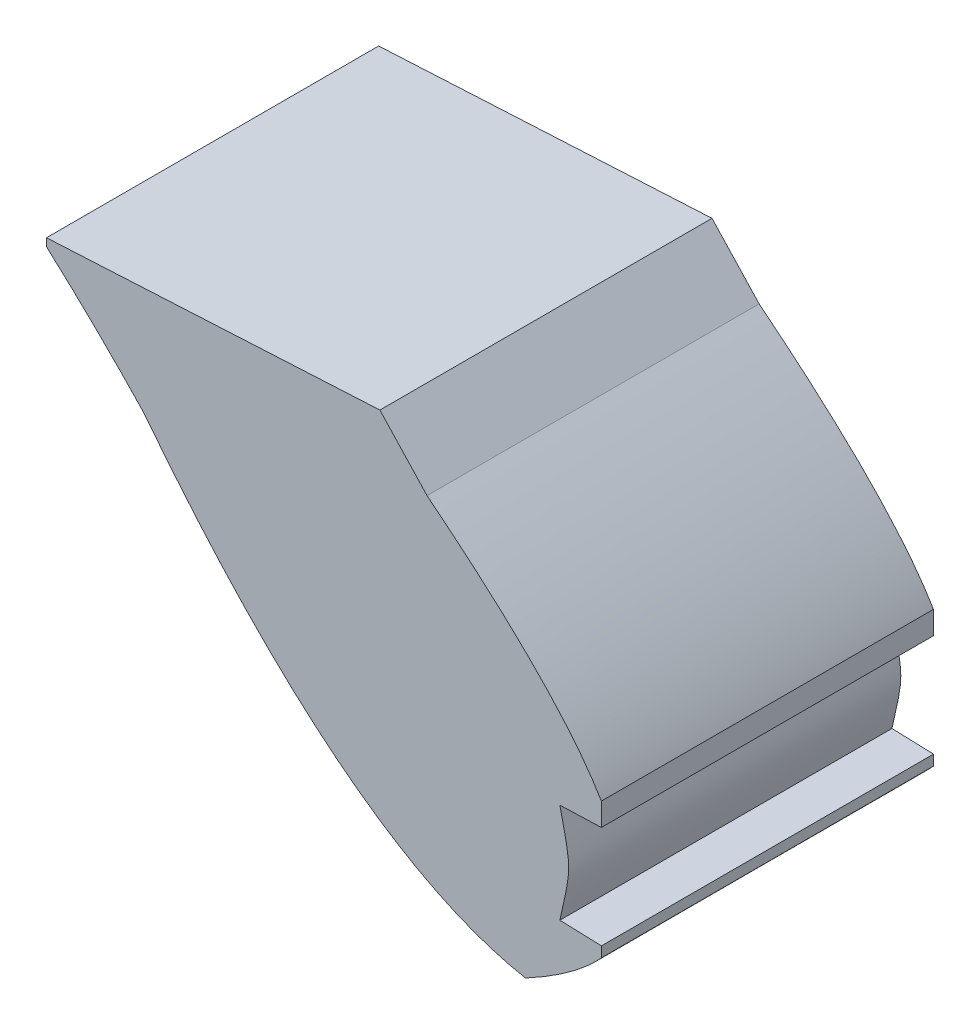
SolidWorks part; units mm, degrees
ref_plane "Alzado" through (0, 0, 0) normal (0, 0, 1) x (1, 0, 0)
ref_plane "Planta" through (0, 0, 0) normal (0, 1, 0) x (1, 0, 0)
ref_plane "Vista lateral" through (0, 0, 0) normal (1, 0, 0) x (0, 0, -1)
sketch "Croquis1" plane through (0, 0, 0) normal (0, 0, 1) x (1, 0, 0)
  line L0 (-8.9818, 12.6082) -> (-23.0359, 11.8716) construction
  line L1 (-8.9818, 12.6082) -> (-23.0359, 11.8716)
  line L2 (-8.9818, 12.6082) -> (-23.0359, 11.8716) construction
  line L4 (-8.9818, 12.6082) -> (-23.0359, 11.8716)
  line L6 (-1.3949, 1.9763) -> (0.3551, 2.2848) construction
  line L7 (-1.3949, 1.9763) -> (0.3551, 2.2848)
  line L8 (0.3551, 2.2848) -> (0.3551, 2.8423) construction
  line L9 (0.3551, 2.2848) -> (0.3551, 3.0015)
  line L10 (0.3551, -2.2848) -> (-1.3949, -2.2237) construction
  line L11 (0.3551, -2.2848) -> (-1.3949, -2.2237)
  line L12 (0.3551, 2.2848) -> (0.3551, -2.2848) construction
  line L13 (0.3551, -2.2848) -> (0.3551, -2.7233)
  line L14 (-8.9818, 12.6082) -> (-6.9949, 10.4774)
  line L15 (-23.0359, 11.5401) -> (-23.0359, 11.8716) construction
  line L16 (-23.0359, 11.5401) -> (-23.0359, 11.8716)
  arc A0 (-18.9452, 7.5409) -> (-23.0359, 11.5401) centre (-69.8841, -40.4718) ccw construction
  arc A1 (-18.9452, 7.5409) -> (-23.0359, 11.5401) centre (-69.8841, -40.4718) ccw
  spline S1 degree 2 poles (-828.7061, 3922.2202) (545.889, -3962.7836) (-262.0834, 3982.5902) knots 0.462185 0.462185 0.462185 0.537731 0.537731 0.537731 weights 1 1 1 only from (-18.9452, 7.5409) to (-2.8466, -5.0591) construction
  spline S2 degree 2 poles (-18.9452, 7.5409) (-10.215, -3.6976) (-2.8466, -5.0591) knots 0.497667 0.497667 0.497667 0.499554 0.499554 0.499554 weights 1 1 1
  spline S3 degree 2 poles (-3804.8689, 1232.5771) (3762.9122, -1369.6643) (-3716.5752, 1504.852) knots 0.462212 0.462212 0.462212 0.537836 0.537836 0.537836 weights 1 1 1 only from (0.3551, 3.0015) to (-6.9949, 10.4774) construction
  spline S4 degree 2 poles (0.3551, 3.0015) (-1.4487, 6.0584) (-6.9949, 10.4774) knots 0.500821 0.500821 0.500821 0.502013 0.502013 0.502013 weights 1 1 1
  spline S5 degree 2 poles (-1.3949, -2.2237) (-0.9075, -0.1237) (-1.3949, 1.9763) knots 0 0 0 1 1 1 weights 1 3.231801 1 construction
  spline S6 degree 2 poles (-1.3949, -2.2237) (-0.9075, -0.1237) (-1.3949, 1.9763) knots 0 0 0 1 1 1 weights 1 3.231801 1
  spline S7 degree 2 poles (-3997.263, 185.0077) (3984.2333, -348.7483) (-3965.0625, 511.2595) knots 0.462205 0.462205 0.462205 0.537778 0.537778 0.537778 weights 1 1 1 only from (-2.8466, -5.0591) to (0.3551, -2.7233) construction
  spline S8 degree 2 poles (-2.8466, -5.0591) (-0.7424, -3.9352) (0.3551, -2.7233) knots 0.498812 0.498812 0.498812 0.499413 0.499413 0.499413 weights 1 1 1
extrude "Saliente-Extruir1" add sketch "Croquis1" along normal mid plane 14 contours S2 S8 L13 L11 S6 L7 L9 S4 L14 L1 L16 A1 region at (-9.5529, 4.8585, 0)
sketch "Croquis3" plane through (0, 0, 0) normal (0, 0, 1) x (1, 0, 0)
  line L0 (-6.742, 0) -> (0, 0) construction
  line L1 (-1.8181, 2) -> (-1.7771, 2.0103) construction
  line L3 (-1.8181, 2) -> (-0.1689, 2.4155) construction
  line L4 (-1.8181, 2) -> (0.3551, 3.0015)
  line L5 (0.3551, 3.0015) -> (0.3551, 0)
  line L6 (-1.9135, -2.1825) -> (0.3551, -2.2848)
  line L7 (0.3551, -2.2848) -> (0.3551, 0)
  parabola Q0 (-1.9135, -2.1825) -> (-1.8181, 2) focus (-3.3181, 0) apex (-1.3181, 0)
  dimension "D1" = 2
  dimension "D2" = 2
extrude "Cortar-Extruir1" [suppressed] cut sketch "Croquis3" against normal through all both and the other way through all
sketch "Croquis4" plane through (0, 0, 0) normal (0, 0, 1) x (1, 0, 0)
  line L0 (-1.3949, 1.9763) -> (0.3551, 2.2848) construction
  line L1 (-1.3949, 1.9763) -> (0.3551, 2.2848)
  line L2 (0.3551, 2.2848) -> (0.3551, 3.0015) construction
  line L3 (0.3551, 2.0374) -> (0.3551, 2.2848)
  line L4 (-1.3949, 1.9763) -> (0.3551, 2.0374)
  line L5 (0, 0) -> (-3.4665, 0) construction
  dimension "D1" = 2
extrude "Saliente-Extruir2" add sketch "Croquis4" along normal through all and the other way through all
sketch "Croquis7" plane through (0, 0, 0) normal (0, 0, 1) x (1, 0, 0)
  line L0 (0, 0) -> (-15.3945, 3.3171) construction
  line L1 (-17.3963, 18.9371) -> (-15.3945, 3.3171) construction
  line L2 (-15.3945, 3.3171) -> (-9.9316, -2.6296) construction
  line L3 (-15.3945, 3.3171) -> (-10.2385, 8.0535) construction
  line L4 (-17.3963, 18.9371) -> (-16.5429, 12.2783) construction
  line L5 (0, 0) -> (-1.3461, -2.2254) construction
  line L6 (-69.8841, 29.5282) -> (-81.9382, 42.5765) construction
  line L7 (-69.8841, 29.5282) -> (-20.9497, 29.5282) construction
  line L8 (-17.8101, 13.1658) -> (-25.5429, 13.1658)
  line L9 (-18.2059, 7.0951) -> (-21.9246, 11.9299) construction
  line L10 (0.3551, -2.5) -> (-2.4497, -2.0473)
  line L11 (-1.3461, -2.2254) -> (-2.0075, -3.6222) construction
  line L12 (-1.3461, -2.2254) -> (-1.4547, -2.8987) construction
  line L13 (-1.3461, -2.2254) -> (-1.2286, -1.4976) construction
  line L14 (0.3551, -2.2848) -> (0.3551, -2.7233) construction
  line L15 (0.3551, -2.2848) -> (-1.3949, -2.2237) construction
  line L16 (-2.0075, -3.6222) -> (-3.0629, -5.8512) construction
  line L17 (-2.6331, -4.9434) -> (-3.7044, -5.5324) construction
  line L18 (-2.6331, -4.9434) -> (-3.2248, -3.867) construction
  line L19 (-2.6331, -4.9434) -> (-2.2174, -6.1341) construction
  line L20 (-4.0838, -4.7637) -> (-1.6363, -5.0668) construction
  line L21 (-4.0838, -4.7637) -> (-0.036, -5.9454) construction
  line L22 (-4.0838, -4.7637) -> (-3.7621, -3.6616) construction
  line L23 (-4.0838, -4.7637) -> (-6.31, -3.7023) construction
  line L24 (-6.31, -3.7023) -> (-8.69, -2.5677) construction
  line L25 (-8.69, -2.5677) -> (-6.8421, -3.7725) construction
  line L26 (-8.69, -2.5677) -> (-7.9481, -1.4297) construction
  line L27 (-10.6884, -0.8477) -> (-8.69, -2.5677) construction
  line L28 (-10.6884, -0.8477) -> (-14.8546, 2.738) construction
  line L29 (-14.8546, 2.738) -> (-14.5337, 2.3989) construction
  line L30 (-14.8546, 2.738) -> (-14.6199, 2.9602) construction
  line L31 (-18.2059, 7.0951) -> (-14.8546, 2.738) construction
  line L32 (-8.9818, 12.6082) -> (-23.0359, 11.8716) construction
  line L33 (-8.9818, 12.6082) -> (-23.0359, 11.8716)
  line L34 (-21.9246, 11.9299) -> (-21.9826, 13.0367) construction
  line L35 (-21.9246, 11.9299) -> (-23.4156, 13.0367) construction
  arc A0 (-18.9452, 7.5409) -> (-23.0359, 11.5401) centre (-69.8841, -40.4718) ccw construction
  spline S0 degree 2 poles (-654.4568, 2937.5195) (409.3679, -2972.9237) (-163.476, 2987.5518) knots 0.467242 0.467242 0.467242 0.532662 0.532662 0.532662 weights 1 1 1 only from (-18.9452, 7.5409) to (-2.8466, -5.0591) construction
  spline S1 degree 2 poles (-18.6263, 7.1332) (-10.0803, -3.7225) (-2.8466, -5.0591) knots 0.497702 0.497702 0.497702 0.499554 0.499554 0.499554 weights 1 1 1 construction
  spline S3 degree 2 poles (-2999.4042, 119.7504) (2988.2948, -261.6206) (-2971.0465, 402.239) knots 0.467267 0.467267 0.467267 0.532713 0.532713 0.532713 weights 1 1 1 only from (-2.8466, -5.0591) to (0.3551, -2.7233) construction
  spline S4 degree 2 poles (-2.8466, -5.0591) (-2.7385, -5.0013) (-2.6331, -4.9434) knots 0.498812 0.498812 0.498812 0.498843 0.498843 0.498843 weights 1 1 1
  dimension "D1" = 2.5
  dimension "D2" = 22
  dimension "D3" = 16.17
  dimension "D4" = 54.138
  dimension "D5" = 34.566
  dimension "D6" = 50.413
sketch "Croquis6" plane through (0, 0, 0) normal (1, 0, 0) x (0, 0, -1)
  line L0 (7, 12.6082) -> (7, 10.4774) construction
  line L1 (7, 12.6082) -> (7, -5.0591)
  line L2 (-7, 12.6082) -> (-7, 10.4774) construction
  line L3 (-7, 12.6082) -> (-7, -5.0591)
  line L4 (-7, -5.0591) -> (7, -5.0591) construction
  line L5 (-7, -5.0591) -> (-5, -5.0591)
  line L6 (7, 12.6082) -> (-12.4533, -5.0591)
  line L7 (-7, 12.6082) -> (-5, -5.0591)
  line L8 (-12.4533, -5.0591) -> (7, -5.0591)
  dimension "D1" = 2
  dimension "D2" = 19.4533
extrude "Cortar-Extruir2" cut sketch "Croquis6" against normal through all and the other way through all rebuild error yes
